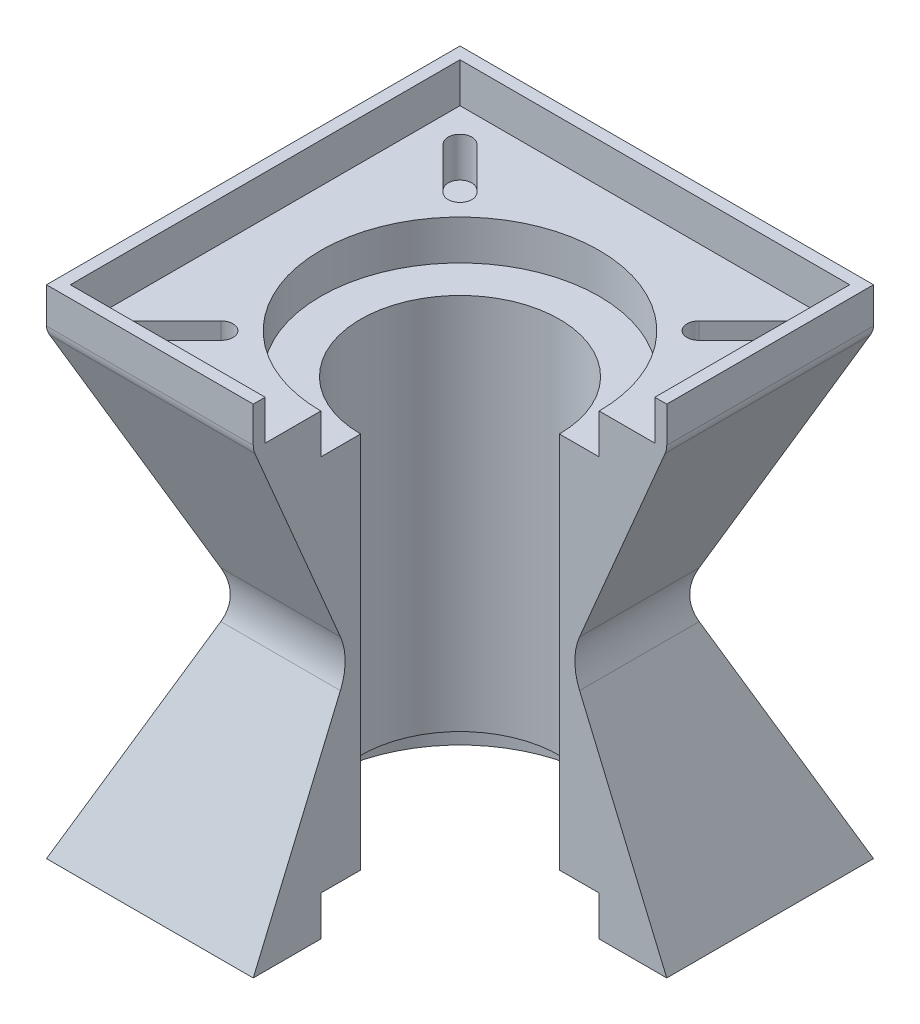
SolidWorks part; units mm, degrees
material "Cast Stainless Steel"
ref_plane "Front Plane" through (0, 0, 0) normal (0, 0, 1) x (1, 0, 0)
ref_plane "Top Plane" through (0, 0, 0) normal (0, 1, 0) x (1, 0, 0)
ref_plane "Right Plane" through (0, 0, 0) normal (1, 0, 0) x (0, 0, -1)
sketch "Sketch4" plane through (0, 0, 0) normal (0, 1, 0) x (1, 0, 0)
  line L1 (-52, 52) -> (52, 52)
  line L2 (-52, 52) -> (-52, -52)
  line L3 (-52, -52) -> (52, -52)
  line L4 (52, 52) -> (52, -52)
  line L5 (-52, 52) -> (52, -52) construction
  line L6 (-52, -52) -> (52, 52) construction
  point P0 (0, 0)
  dimension "D1" = 104
  dimension "D2" = 104
extrude "Boss-Extrude4" add sketch "Sketch4" along normal blind 57.5 draft 23
mirror "Mirror2" about plane through (0, 57.5, 0) normal (0, 1, 0) of bodies 108
sketch "Sketch6" plane through (0, 115, 0) normal (0, 1, 0) x (1, 0, 0)
  circle A0 centre (0, 0) radius 25
  dimension "D1" = 50
extrude "Cut-Extrude4" cut sketch "Sketch6" against normal blind 219.5
sketch "Sketch7" plane through (0, 115, 0) normal (0, 1, 0) x (1, 0, 0)
  circle A0 centre (0, 0) radius 35
  dimension "D1" = 70
extrude "Cut-Extrude5" cut sketch "Sketch7" against normal blind 10
sketch "Sketch8" plane through (0, 0, 0) normal (0, -1, 0) x (1, 0, 0)
  circle A0 centre (0, 0) radius 35
  dimension "D1" = 70
extrude "Cut-Extrude6" cut sketch "Sketch8" against normal blind 10
fillet "Fillet1" radius 15 4 edges at (0, 57.5, -27.5927) (27.5927, 57.5, 0) (-27.5927, 57.5, 0) (0, 57.5, 27.5927)
sketch "Sketch9" plane through (0, 115, 0) normal (0, 1, 0) x (1, 0, 0)
  line L0 (0, 0) -> (0, -52) construction
  line L1 (-52, -52) -> (52, -52) construction
  line L2 (0, 0) -> (52, 0) construction
  line L3 (52, -52) -> (52, 52) construction
  line L4 (52, -52) -> (52, 0)
  line L5 (0, -52) -> (52, -52)
  line L6 (52, 0) -> (25, 0)
  line L7 (0, -52) -> (0, -25)
  circle A0 centre (0, 0) radius 25 construction
  arc A1 (0, -25) -> (25, 0) centre (0, 0) ccw
  circle A2 centre (0, 0) radius 35 construction
  arc A3 (0, -35) -> (35, 0) centre (0, 0) ccw
extrude "Cut-Extrude7" cut sketch "Sketch9" against normal blind 144 contours A1 L6 L4 L5 L7
sketch "Sketch10" plane through (0, 115, 0) normal (0, 1, 0) x (1, 0, 0)
  line L6 (0, -52) -> (0, -35) construction
  line L7 (0, -52) -> (0, -49)
  line L8 (52, 0) -> (35, 0) construction
  line L9 (52, 0) -> (49, 0)
  line L12 (-3, -49) -> (-3, -37.8814)
  line L13 (37.8814, 3) -> (49, 3)
  line L14 (49, 3) -> (49, 49)
  line L15 (49, 49) -> (-49, 49)
  line L16 (-49, 49) -> (-49, -49)
  line L17 (-49, -49) -> (-3, -49)
  line L20 (49, 0) -> (49, 49)
  line L21 (49, 49) -> (-49, 49)
  line L22 (-49, 49) -> (-49, -49)
  line L23 (-49, -49) -> (0, -49)
  line L24 (0, -52) -> (0, -35)
  line L25 (35, 0) -> (52, 0)
  line L26 (52, 0) -> (52, 52)
  line L27 (52, 52) -> (-52, 52)
  line L28 (-52, 52) -> (-52, -52)
  line L29 (-52, -52) -> (0, -52)
  line L32 (52, 0) -> (52, 52)
  line L33 (52, 52) -> (-52, 52)
  line L34 (-52, 52) -> (-52, -52)
  line L35 (-52, -52) -> (0, -52)
  arc A2 (37.8814, 3) -> (-3, -37.8814) centre (0, 0) ccw
  arc A4 (35, 0) -> (0, -35) centre (0, 0) ccw
  point P2 (49, 0)
  point P7 (0, -49)
  dimension "D1" = 3
  dimension "D2" = 0
extrude "Boss-Extrude5" add sketch "Sketch10" along normal blind 10
fillet "Fillet2" radius 5 4 edges at (0, 115, -52) (52, 115, -26) (-52, 115, 0) (-26, 115, 52)
sketch "Sketch11" plane through (0, 115, 0) normal (0, 1, 0) x (1, 0, 0)
  line L0 (0, 0) -> (-52, 52) construction
  line L1 (-40.6586, 40.6586) -> (-30.052, 30.052) construction
  line L2 (-38.5373, 42.78) -> (-27.9307, 32.1734)
  line L3 (-42.78, 38.5373) -> (-32.1734, 27.9307)
  line L4 (38.5373, 42.78) -> (27.9307, 32.1734)
  line L5 (42.78, 38.5373) -> (32.1734, 27.9307)
  line L6 (40.6586, 40.6586) -> (30.052, 30.052) construction
  line L7 (42.78, -38.5373) -> (32.1734, -27.9307)
  line L8 (38.5373, -42.78) -> (27.9307, -32.1734)
  line L9 (40.6586, -40.6586) -> (30.052, -30.052) construction
  line L10 (-38.5373, -42.78) -> (-27.9307, -32.1734)
  line L11 (-42.78, -38.5373) -> (-32.1734, -27.9307)
  line L12 (-40.6586, -40.6586) -> (-30.052, -30.052) construction
  circle A0 centre (0, 0) radius 50 construction
  arc A1 (-38.5373, 42.78) -> (-42.78, 38.5373) centre (-40.6586, 40.6586) ccw
  arc A2 (-32.1734, 27.9307) -> (-27.9307, 32.1734) centre (-30.052, 30.052) ccw
  arc A3 (42.78, 38.5373) -> (38.5373, 42.78) centre (40.6586, 40.6586) ccw
  arc A4 (27.9307, 32.1734) -> (32.1734, 27.9307) centre (30.052, 30.052) ccw
  arc A5 (38.5373, -42.78) -> (42.78, -38.5373) centre (40.6586, -40.6586) ccw
  arc A6 (32.1734, -27.9307) -> (27.9307, -32.1734) centre (30.052, -30.052) ccw
  arc A7 (-42.78, -38.5373) -> (-38.5373, -42.78) centre (-40.6586, -40.6586) ccw
  arc A8 (-27.9307, -32.1734) -> (-32.1734, -27.9307) centre (-30.052, -30.052) ccw
  point P3 (-35.3553, 35.3553)
  point P8 (-35.3553, 35.3553)
  point P13 (0, 0)
  point P14 (0, 0)
  point P18 (35.3553, 35.3553)
  point P25 (35.3553, -35.3553)
  point P32 (-35.3553, -35.3553)
  point P37 (0, 0)
  dimension "D1" = 100
  dimension "D3" = 3
  dimension "D2" = 15
  dimension "D4" = 4
extrude "Cut-Extrude8" cut sketch "Sketch11" against normal blind 10
equation "\"A\"= 115mm"
equation "\"B\"= 104mm"
equation "\"C\"= 23deg"
equation "\"D1@Sketch4\"=\"B\""
equation "\"D2@Sketch4\"=\"B\""
equation "\"D1@Boss-Extrude4\"=\"A\"/2"
equation "\"D3@Boss-Extrude4\"=\"C\""
